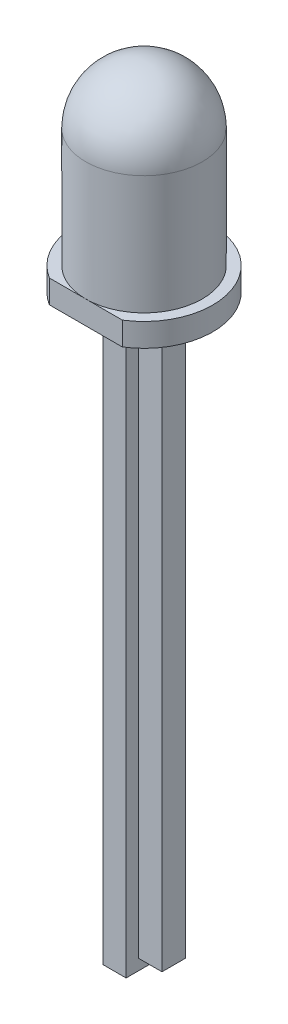
SolidWorks part; units mm, degrees
ref_plane "Front Plane" through (0, 0, 0) normal (0, 0, 1) x (1, 0, 0)
ref_plane "Top Plane" through (0, 0, 0) normal (0, 1, 0) x (1, 0, 0)
ref_plane "Right Plane" through (0, 0, 0) normal (1, 0, 0) x (0, 0, -1)
sketch "Sketch1" plane through (0, 0, 0) normal (0, 1, 0) x (1, 0, 0)
  line L5 (-0.5, 0.5) -> (2.04, 0.5)
  line L6 (-0.5, 0.5) -> (-0.5, -0.5)
  line L7 (-0.5, -0.5) -> (2.04, -0.5)
  line L8 (2.04, 0.5) -> (2.04, -0.5)
  dimension "D1" = 0.5
  dimension "D2" = 0.5
  dimension "D3" = 2.54
  dimension "D4" = 0.5
extrude "Base-Extrude" add sketch "Sketch1" along normal blind 0.381
sketch "Sketch2" plane through (0, 0, 0) normal (0, -1, 0) x (1, 0, 0)
  line L0 (2.04, -0.5) -> (-0.5, -0.5) construction
  line L1 (-0.5, 0.5) -> (0.5, 0.5)
  line L2 (-0.5, 0.5) -> (-0.5, -0.5)
  line L3 (-0.5, -0.5) -> (0.5, -0.5)
  line L4 (0.5, 0.5) -> (0.5, -0.5)
  line L6 (2.04, 0.5) -> (1.04, 0.5)
  line L7 (2.04, 0.5) -> (2.04, -0.5)
  line L8 (2.04, -0.5) -> (1.04, -0.5)
  line L9 (1.04, 0.5) -> (1.04, -0.5)
extrude "Boss-Extrude1" add sketch "Sketch2" along normal blind 24
sketch "Sketch7" plane through (0, -24, 0) normal (0, -1, 0) x (1, 0, 0)
  line L4 (-0.5, 0.5) -> (-0.5, -0.5)
  line L5 (-0.5, -0.5) -> (0.5, -0.5)
  line L6 (0.5, -0.5) -> (0.5, 0.5)
  line L7 (0.5, 0.5) -> (-0.5, 0.5)
  line L8 (-0.5, 0.5) -> (-0.5, -0.5)
  line L9 (-0.5, -0.5) -> (0.5, -0.5)
  line L10 (0.5, -0.5) -> (0.5, 0.5)
  line L11 (0.5, 0.5) -> (-0.5, 0.5)
  dimension "D1" = 0
extrude "Boss-Extrude4" add sketch "Sketch7" along normal blind 1
fillet "Fillet5" radius 0.254 4 edges at (-0.5, 0.381, 0) (2.04, 0.381, 0) (1.04, 0, 0)
sketch "Sketch3" plane through (0, 0.381, 0) normal (0, 1, 0) x (-1, 0, 0)
  line L0 (-0.77, 0) -> (-0.77, 0.5) construction
  line L1 (0.246, 0.5) -> (-1.786, 0.5) construction
  line L2 (-0.77, 0) -> (-2.04, 0) construction
  line L3 (-2.04, 0.5) -> (-2.04, -0.5) construction
  line L4 (-2.336, 2.5) -> (0.796, 2.5)
  arc A0 (-2.336, 2.5) -> (0.796, 2.5) centre (-0.77, 0) ccw
  circle A1 centre (-0.77, 0) radius 2.5 construction
  dimension "D1" = 5.9
  dimension "D2" = 5
extrude "Boss-Extrude2" add sketch "Sketch3" along normal blind 1
sketch "Sketch4" plane through (0, 1.381, 0) normal (0, 1, 0) x (-1, 0, 0)
  line L0 (0.796, 2.5) -> (-2.336, 2.5) construction
  circle A0 centre (-0.77, 0) radius 2.5
extrude "Boss-Extrude3" add sketch "Sketch4" along normal blind 7.6
fillet "Fillet4" radius 2.5 1 edges at (0.77, 8.981, 2.5) tangent propagation no
sketch "Sketch6" plane through (0, 0, 0.5) normal (0, 0, 1) x (1, 0, 0)
  line L0 (-0.246, 0.381) -> (1.786, 0.381) construction
  line L1 (0.754, 0.381) -> (0.786, 0.381)
  line L2 (0.754, 0.381) -> (0.754, 0)
  line L3 (0.754, 0) -> (0.786, 0)
  line L4 (0.786, 0.381) -> (0.786, 0)
extrude "Cut-Extrude1" cut sketch "Sketch6" against normal through all
sketch "Component_Outline" plane through (0, 0, 0) normal (0, 1, 0) x (1, 0, 0)
  line L0 (-0.796, -2.5) -> (2.336, -2.5)
  arc A0 (2.336, -2.5) -> (-0.796, -2.5) centre (0.77, 0) ccw
  arc A1 (2.336, -2.5) -> (-0.796, -2.5) centre (0.77, 0) ccw construction
